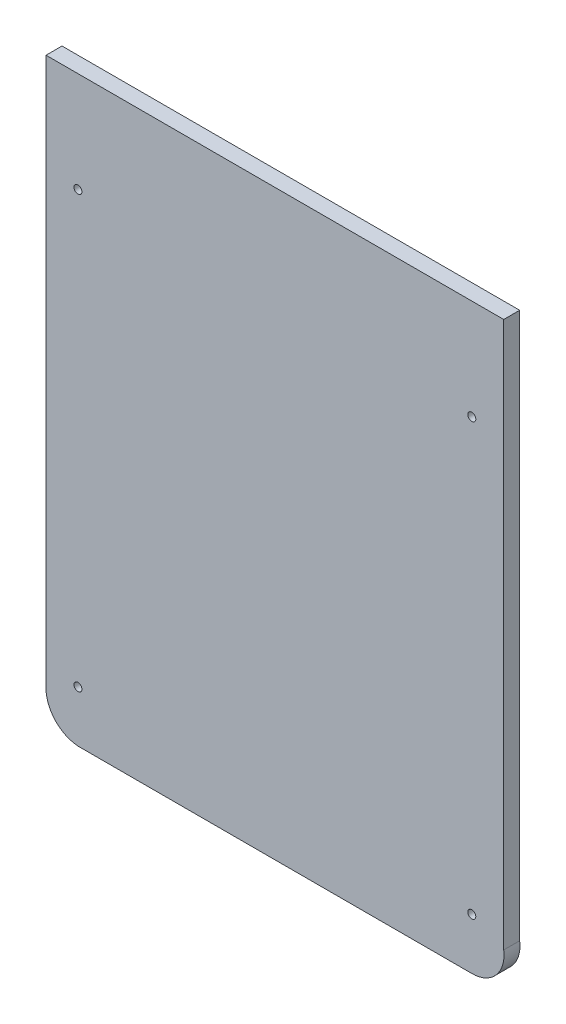
SolidWorks part; units mm, degrees
material "Beech"
ref_plane "Front Plane" through (0, 0, 0) normal (0, 0, 1) x (1, 0, 0)
ref_plane "Top Plane" through (0, 0, 0) normal (0, 1, 0) x (1, 0, 0)
ref_plane "Right Plane" through (0, 0, 0) normal (1, 0, 0) x (0, 0, -1)
sketch "Sketch1" plane through (0, 0, 0) normal (0, 0, 1) x (1, 0, 0)
  line L0 (-19.05, 903.0272) -> (-19.05, 155.124) construction
  line L1 (163.1, 903.0272) -> (163.1, 155.124) construction
  line L2 (-19.05, 920.1747) -> (163.1, 920.1747)
  line L5 (163.1, 683.9522) -> (163.1, 855.4022) construction
  line L6 (-6.35, 688.3997) -> (150.4, 688.3997)
  line L7 (163.1, 702.8437) -> (163.1, 920.1747)
  line L10 (-19.05, 920.1747) -> (-19.05, 701.0997)
  arc A2 (-19.05, 701.0997) -> (-6.35, 688.3997) centre (-5.3248, 702.1249) ccw
  arc A3 (150.4, 688.3997) -> (163.1, 702.8437) centre (150.5204, 701.0991) ccw
extrude "Boss-Extrude1" add sketch "Sketch1" along normal blind 6.35
hole_wizard "Hole1" positions "Sketch2" profile "Sketch3" legacy
sketch "Sketch2" plane through (72.025, -412.7928, 19.05) normal (0, 0, 1) x (1, 0, 0)
  point P0 (-78.375, 1293.0392)
  point P3 (-78.375, 1121.5892)
  point P6 (78.375, 1121.5892)
  point P9 (78.375, 1293.0392)
  point P12 (-764.0155, 1530.0782)
sketch "Sketch3" plane through (-6.35, 880.2464, 19.05) normal (1, 0, 0) x (0, -1, 0)
  line L0 (0, 0) -> (0, 32.7039)
  line L1 (0, 32.7039) -> (1.5875, 31.75)
  line L2 (1.5875, 31.75) -> (1.5875, 4.0177)
  line L3 (1.5875, 4.0177) -> (5.08, 0)
  line L4 (5.08, 0) -> (0, 0)
  line L5 (0, -14.3089) -> (0, 102.4216) construction
  line L6 (0, 32.7039) -> (-1.5875, 31.75) construction
  line L7 (-1.5875, 4.0177) -> (-5.08, 0) construction
  dimension "Diameter" = 3.175
  dimension "Depth" = 31.75
  dimension "C-Sink Diameter" = 10.16
  dimension "C-Sink Angle" = 82
  dimension "Drill Angle" = 118
